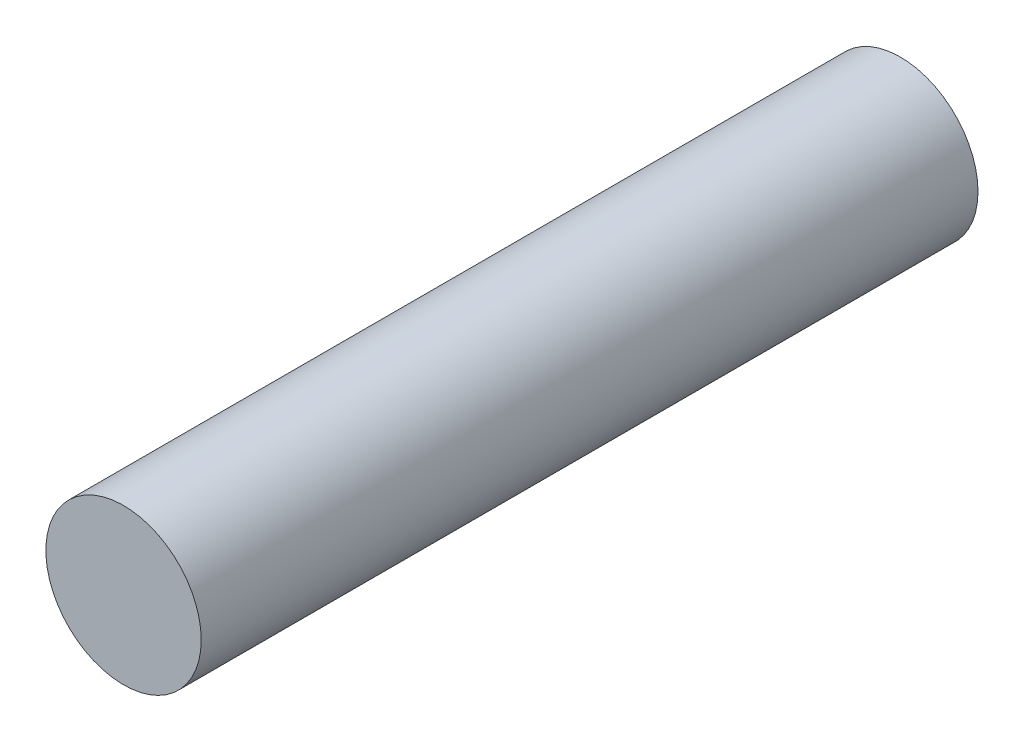
SolidWorks part; units mm, degrees
ref_plane "Front Plane" through (0, 0, 0) normal (0, 0, 1) x (1, 0, 0)
ref_plane "Top Plane" through (0, 0, 0) normal (0, 1, 0) x (1, 0, 0)
ref_plane "Right Plane" through (0, 0, 0) normal (1, 0, 0) x (0, 0, -1)
sketch "Sketch1" plane through (0, 0, 0) normal (0, 0, 1) x (1, 0, 0)
  circle A0 centre (0, 0) radius 3.175
  dimension "D1" = 6.35
extrude "Boss-Extrude1" add sketch "Sketch1" along normal blind 31.75
sketch "Sketch2" plane through (0, 0, 0) normal (0, 0, -1) x (-1, 0, 0)
  point P0 (0, 0)
